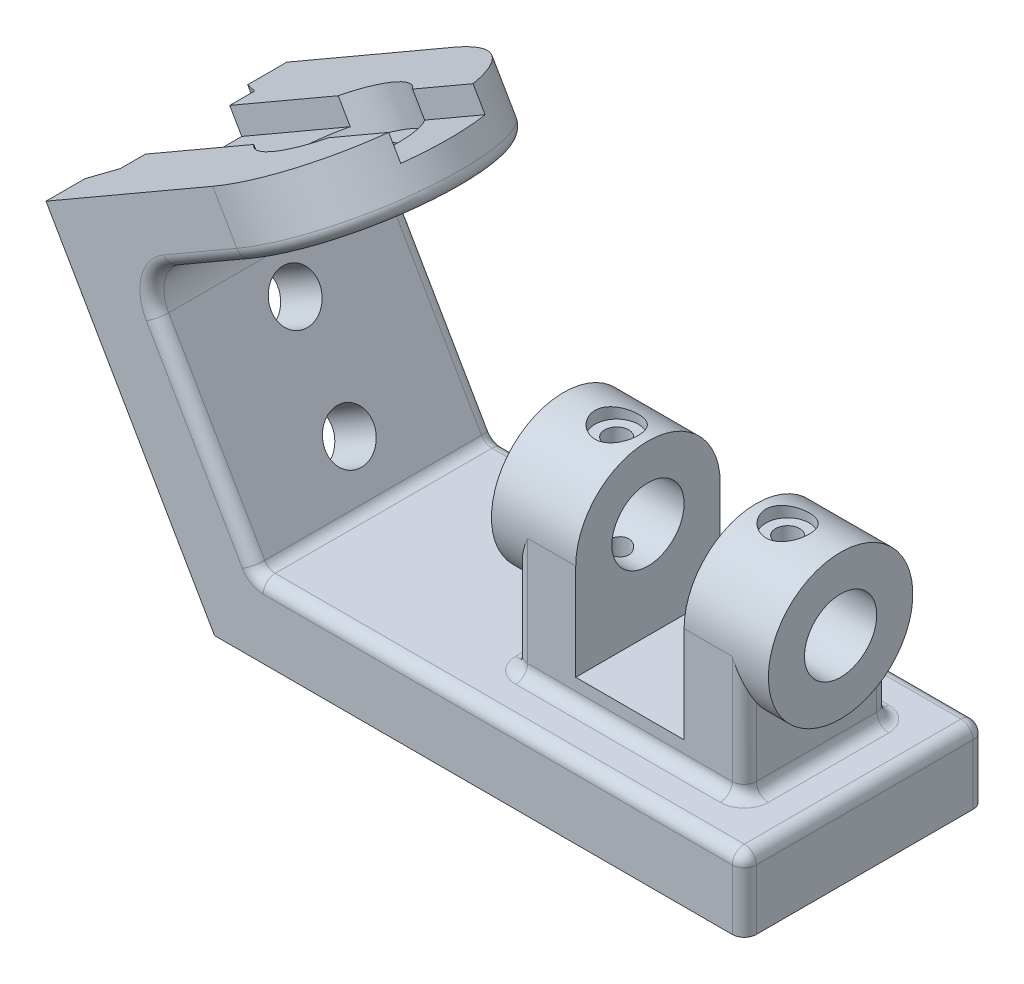
SolidWorks part; units mm, degrees
material "AISI 1035 Steel (SS)"
ref_plane "Front Plane" through (0, 0, 0) normal (0, 0, 1) x (1, 0, 0)
ref_plane "Top Plane" through (0, 0, 0) normal (0, 1, 0) x (1, 0, 0)
ref_plane "Right Plane" through (0, 0, 0) normal (1, 0, 0) x (0, 0, -1)
sketch "Sketch1" plane through (0, 0, 0) normal (0, 0, 1) x (1, 0, 0)
  line L0 (0, 0) -> (139.7, 0)
  line L1 (139.7, 0) -> (139.7, 19.05)
  line L2 (139.7, 19.05) -> (10.9985, 19.05)
  line L3 (10.9985, 19.05) -> (-20.0147, 72.7665)
  line L4 (-20.0147, 72.7665) -> (7.4816, 88.6415)
  line L5 (7.4816, 88.6415) -> (-0.4559, 102.3897)
  line L6 (-0.4559, 102.3897) -> (-44.45, 76.9897)
  line L7 (0, 0) -> (-44.45, 76.9897)
  dimension "D1" = 120
  dimension "D2" = 19.05
  dimension "D3" = 19.05
  dimension "D4" = 15.875
  dimension "D5" = 139.7
  dimension "D6" = 88.9
  dimension "D7" = 50.8
extrude "Boss-Extrude1" add sketch "Sketch1" along normal mid plane 63.5
sketch "Sketch2" plane through (-44.45, 76.9897, 0) normal (-0.5, 0.866, 0) x (0.866, 0.5, 0)
  line L0 (50.8, -31.75) -> (50.8, 31.75) construction
  circle A0 centre (50.8, 0) radius 31.75
extrude "Boss-Extrude2" add sketch "Sketch2" against normal blind 15.875
sketch "Sketch4" plane through (-44.45, 76.9897, 0) normal (-0.5, 0.866, 0) x (0.866, 0.5, 0)
  circle A0 centre (50.8, 0) radius 9.525
  dimension "D1" = 19.05
extrude "Cut-Extrude1" cut sketch "Sketch4" against normal up to next
sketch "Sketch5" plane through (-44.45, 76.9897, 0) normal (-0.5, 0.866, 0) x (0.866, 0.5, 0)
  circle A0 centre (50.8, 0) radius 15.875
  dimension "D1" = 31.75
extrude "Cut-Extrude2" cut sketch "Sketch5" against normal blind 9.525
sketch "Sketch6" plane through (0, 0, 0) normal (-0.866, -0.5, 0) x (0, 0, 1)
  line L5 (-11.1252, 88.9) -> (-11.1252, 82.55)
  line L6 (31.75, 88.9) -> (-31.75, 88.9) construction
  line L7 (-11.1252, 82.55) -> (11.1252, 82.55)
  line L8 (11.1252, 82.55) -> (11.1252, 88.9)
  line L9 (11.1252, 88.9) -> (-11.1252, 88.9)
  point P5 (0, 82.55)
  point P10 (0, 88.9)
  dimension "D1" = 6.35
  dimension "D2" = 22.2504
extrude "Cut-Extrude3" cut sketch "Sketch6" against normal through all
sketch "Sketch7" plane through (-44.45, 76.9897, 0) normal (-0.5, 0.866, 0) x (0.866, 0.5, 0)
  line L0 (0, 21.4376) -> (6.4323, 17.7239)
  line L1 (0, 11.1252) -> (0, 31.75) construction
  line L2 (6.4323, 17.7239) -> (6.4323, -17.7239)
  line L3 (6.4323, -17.7239) -> (0, -21.4376)
  line L4 (0, -31.75) -> (0, -11.1252) construction
  line L5 (0, -21.4376) -> (0, 21.4376)
  point P4 (0, 0)
  dimension "D2" = 120
  dimension "D3" = 120
  dimension "D4" = 6.4323
extrude "Cut-Extrude4" cut sketch "Sketch7" against normal through all
sketch "Sketch8" plane through (5.5706, 3.2162, 0) normal (-0.866, -0.5, 0) x (0, 0, 1)
  line L0 (-11.1252, 82.55) -> (11.1252, 82.55) construction
  circle A0 centre (0, 53.975) radius 6.35
  circle A1 centre (0, 25.4) radius 6.35
  dimension "D1" = 28.575
  dimension "D3" = 12.7
  dimension "D4" = 12.7
  dimension "D2" = 28.575
extrude "Cut-Extrude5" cut sketch "Sketch8" against normal through all
sketch "Sketch9" plane through (0, 0, 0) normal (0, 0, 1) x (1, 0, 0)
  line L0 (66.675, 19.05) -> (66.675, 50.8)
  line L1 (139.7, 19.05) -> (10.9985, 19.05) construction
  line L2 (66.675, 50.8) -> (82.55, 50.8)
  line L3 (82.55, 50.8) -> (82.55, 25.4)
  line L4 (82.55, 25.4) -> (111.125, 25.4)
  line L5 (111.125, 25.4) -> (111.125, 50.8)
  line L6 (111.125, 50.8) -> (127, 50.8)
  line L7 (127, 50.8) -> (127, 19.05)
  line L8 (127, 19.05) -> (66.675, 19.05)
  line L9 (139.7, 0) -> (139.7, 19.05) construction
  point P12 (96.8375, 19.05)
  dimension "D4" = 15.875
  dimension "D1" = 12.7
  dimension "D2" = 60.325
  dimension "D3" = 15.875
  dimension "D5" = 6.35
  dimension "D6" = 25.4
extrude "Boss-Extrude3" add sketch "Sketch9" along normal mid plane 38.1
sketch "Sketch15" plane through (82.55, 0, 0) normal (1, 0, 0) x (0, 0, -1)
  line L0 (-19.05, 50.8) -> (19.05, 50.8) construction
  circle A0 centre (0, 50.8) radius 19.05
extrude "Boss-Extrude6" add sketch "Sketch15" against normal blind 22.225
sketch "Sketch16" plane through (111.125, 0, 0) normal (-1, 0, 0) x (0, 0, 1)
  line L0 (19.05, 50.8) -> (-19.05, 50.8) construction
  circle A0 centre (0, 50.8) radius 19.05
extrude "Boss-Extrude7" add sketch "Sketch16" against normal blind 22.225
sketch "Sketch17" plane through (133.35, 0, 0) normal (1, 0, 0) x (0, 0, -1)
  circle A0 centre (0, 50.8) radius 9.525
  dimension "D1" = 19.05
extrude "Cut-Extrude7" cut sketch "Sketch17" against normal up to surface (73.025 mm away) up to face at (60.325, 50.8, -19.05)
sketch "Sketch18" plane through (0, 0, 0) normal (0, -1, 0) x (1, 0, 0)
  line L0 (139.7, 31.75) -> (139.7, -31.75) construction
  line L2 (0, -31.75) -> (139.7, -31.75) construction
  circle A0 centre (119.38, 0) radius 3.175
  circle A1 centre (74.295, 0) radius 3.175
  point P9 (0, 0)
  dimension "D1" = 45.085
  dimension "D3" = 6.35
  dimension "D4" = 31.75
  dimension "D2" = 20.32
extrude "Cut-Extrude8" cut sketch "Sketch18" against normal through all contours A1 | A0
ref_plane "Plane1" through (0, 66.675, 0) normal (0, -1, 0) x (-1, 0, 0)
sketch "Sketch23" plane through (0, 66.675, 0) normal (0, -1, 0) x (-1, 0, 0)
  circle A0 centre (-74.295, 0) radius 5.715
  circle A1 centre (-119.38, 0) radius 5.715
  dimension "D1" = 11.43
extrude "Cut-Extrude10" cut sketch "Sketch23" against normal through all
fillet "Fillet1" radius 9.525 1 edges at (-20.0147, 72.7665, 0)
fillet "Fillet2" radius 3.175 21 edges at (-2.1268, 41.7838, -31.75) (-16.2038, 71.7454, -31.75) (-2.1421, 83.0853, -31.75) (34.9779, 104.5165, 0) (-2.1421, 83.0853, 31.75) (-16.2038, 71.7454, 31.75) (96.8375, 19.05, -19.05) (66.675, 19.05, 0) (96.8375, 19.05, 19.05) (139.7, 19.05, 0) (75.3493, 19.05, 31.75) (10.9985, 19.05, 0) (75.3493, 19.05, -31.75) (127, 19.05, 0) (127, 34.925, 19.05) (127, 34.925, -19.05) (139.7, 9.525, -31.75) (139.7, 9.525, 31.75) (66.675, 34.925, -19.05) (66.675, 34.925, 19.05) (-2.1268, 41.7838, 31.75)
equation "\"D3@Sketch1\"=\"D2@Sketch1\""
equation "\"D4@Sketch9\"=\"D3@Sketch9\""
